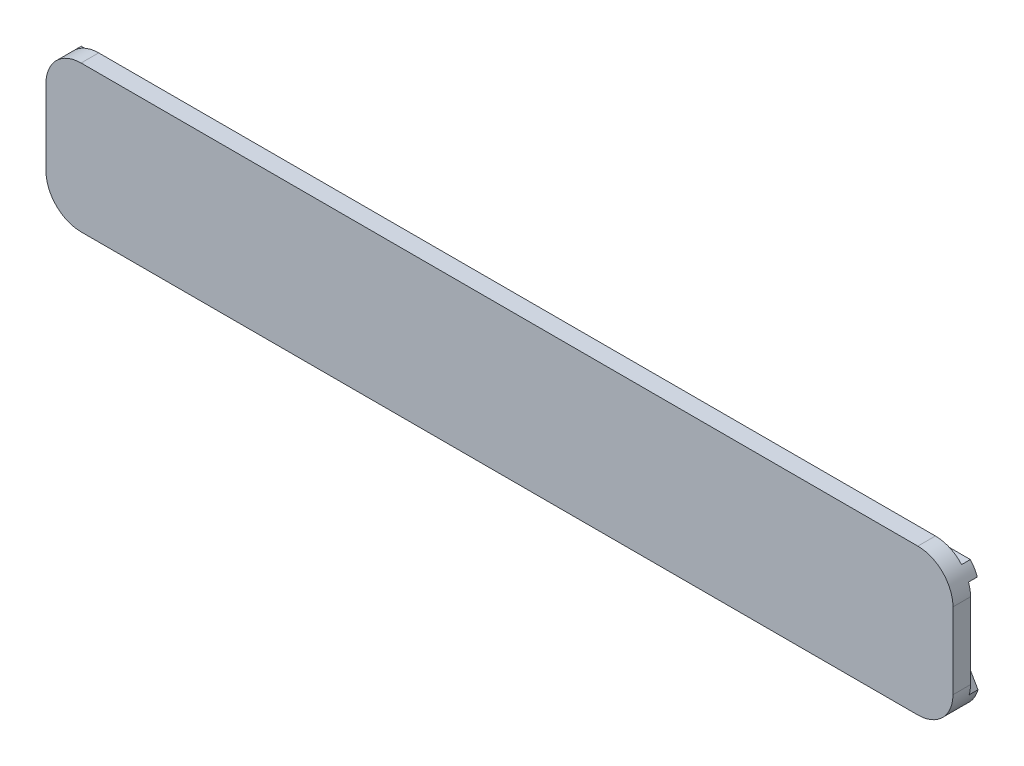
SolidWorks part; units mm, degrees
ref_plane "Front Plane" through (0, 0, 0) normal (0, 0, 1) x (1, 0, 0)
ref_plane "Top Plane" through (0, 0, 0) normal (0, 1, 0) x (1, 0, 0)
ref_plane "Right Plane" through (0, 0, 0) normal (1, 0, 0) x (0, 0, -1)
sketch "Sketch1" plane through (0, 0, 0) normal (0, 0, 1) x (1, 0, 0)
  line L0 (0, 0) -> (55.7, 0) construction
  line L1 (-49.65, 12.5) -> (105.35, 12.5)
  line L2 (-49.65, 12.5) -> (-49.65, -12.5)
  line L3 (-49.65, -12.5) -> (105.35, -12.5)
  line L4 (105.35, 12.5) -> (105.35, -12.5)
  circle A0 centre (55.7, 0) radius 3 construction
  circle A1 centre (0, 0) radius 3 construction
  circle A2 centre (55.7, 0) radius 3 construction
  circle A3 centre (0, 0) radius 3 construction
  circle A4 centre (0, 0) radius 3.3
  circle A5 centre (55.7, 0) radius 3.3
  point P14 (27.85, 0)
  point P15 (27.85, 12.5)
  point P16 (105.35, 0)
  dimension "D2" = 25
  dimension "D3" = 155
  dimension "D1" = 0.3
extrude "Boss-Extrude1" add sketch "Sketch1" against normal blind 2
sketch "Sketch2" plane through (0, 0, 0) normal (0, 0, 1) x (1, 0, 0)
  line L4 (-49.65, 12.5) -> (-49.65, -12.5)
  line L5 (-49.65, -12.5) -> (105.35, -12.5)
  line L6 (105.35, -12.5) -> (105.35, 12.5)
  line L7 (105.35, 12.5) -> (-49.65, 12.5)
  line L8 (-49.65, 12.5) -> (-49.65, -12.5)
  line L9 (-49.65, -12.5) -> (105.35, -12.5)
  line L10 (105.35, -12.5) -> (105.35, 12.5)
  line L11 (105.35, 12.5) -> (-49.65, 12.5)
  dimension "D1" = 0
extrude "Boss-Extrude2" add sketch "Sketch2" along normal blind 1
sketch "Sketch5" plane through (0, 0, -2) normal (0, 0, -1) x (-1, 0, 0)
  line L0 (-105.35, 0) -> (49894.65, 0) construction
  line L1 (-105.35, -12.5) -> (-105.35, 12.5) construction
  line L2 (49.65, 12.5) -> (49.65, -12.5) construction
  line L3 (-27.85, -10.5) -> (-27.85, -8.5)
  line L4 (-105.35, 10.5) -> (-27.85, 10.5)
  line L5 (-105.35, 10.5) -> (-105.35, 8.5)
  line L6 (-105.35, 8.5) -> (-95.535, 8.5)
  line L7 (-27.85, 10.5) -> (-27.85, 8.5)
  line L8 (-103.0406, -8.5) -> (-81.4107, -8.5)
  line L9 (-105.35, -10.5) -> (-105.35, -8.5)
  line L10 (-105.35, -10.5) -> (-27.85, -10.5)
  line L11 (-105.35, 12.5) -> (49.65, 12.5) construction
  line L12 (-105.35, -8.5) -> (-95.535, 8.5)
  line L13 (-93.2256, 8.5) -> (-91.2256, 8.5)
  line L14 (-88.9162, 8.5) -> (-79.1013, -8.5)
  line L15 (-79.1013, -8.5) -> (-77.1013, -8.5)
  line L16 (-74.7919, -8.5) -> (-64.9769, 8.5)
  line L17 (-103.0406, -8.5) -> (-93.2256, 8.5)
  line L18 (-93.2256, 8.5) -> (-91.2256, 8.5)
  line L19 (-91.2256, 8.5) -> (-81.4107, -8.5)
  line L20 (-77.1013, -8.5) -> (-67.2863, 8.5)
  line L21 (-40.9744, 8.5) -> (-31.1594, -8.5)
  line L23 (-28.85, -8.5) -> (-38.665, 8.5)
  line L25 (-93.2256, 8.5) -> (-91.2256, 8.5)
  line L26 (-88.9162, 8.5) -> (-67.2863, 8.5)
  line L27 (-79.1013, -8.5) -> (-77.1013, -8.5)
  line L28 (-74.7919, -8.5) -> (-49.6, -8.5)
  line L29 (-64.9769, 8.5) -> (-45.0449, 8.5)
  line L30 (-38.665, 8.5) -> (-27.85, 8.5)
  line L31 (-28.85, -8.5) -> (-27.85, -8.5)
  line L32 (-45.0449, 8.5) -> (-49.6, -8.5)
  line L34 (-47.5295, -8.5) -> (-42.9744, 8.5)
  line L35 (-42.9744, 8.5) -> (-40.9744, 8.5)
  line L36 (-47.5295, -8.5) -> (-31.1594, -8.5)
  point P4 (-105.35, 0)
  point P7 (49.65, 0)
  point P34 (-27.85, 12.5)
  line M32 (-105.35, 12.5) -> (-105.35, -12.5)
  dimension "D1" = 2
  dimension "D2" = 2
  dimension "D3" = 2
  dimension "D4" = 2
  dimension "D5" = 2
  dimension "D6" = 2
  dimension "D7" = 60
  dimension "D8" = 2
  dimension "D9" = 1
  dimension "D10" = 2
  dimension "D11" = 45
extrude "Boss-Extrude4" add sketch "Sketch5" along normal blind 1.5 contours L12 L0 L17 L13 L19 L14 L26 L20 L16 L29 L21 L23 L30 L7 L4 L6 M32 | L0 L12 L10 L3 L31 L23 L21 L28 L16 L20 L15 L14 L19 L8 L17 M32 region at (66.9728, 7.4905, -2) region at (99.2878, -0.7821, -2)
ref_plane "Plane1" through (27.85, 0, 0) normal (1, 0, 0) x (0, 0, -1)
mirror "Mirror1" about plane through (27.85, 0, 0) normal (1, 0, 0) of "Boss-Extrude4"
fillet "Fillet1" radius 6 4 edges at (105.35, 12.5, -0.5) (105.35, -12.5, -0.5) (-49.65, -12.5, -0.5) (-49.65, 12.5, -0.5)
sketch "Sketch3" plane through (0, 0, 1) normal (0, 0, 1) x (1, 0, 0)
  line L0 (-49.65, -5) -> (105.35, -5) construction
  line L1 (-43.65, -12.5) -> (99.35, -12.5) construction
  line L2 (-49.65, 6.5) -> (-49.65, -6.5) construction
  text T0 "ED Robotics" font "Century Gothic" height 10
  point P7 (27.85, -12.5)
  point P8 (27.85, -5)
  point P9 (-15.5966, -4.6628)
  point P10 (0, 0)
  dimension "D1" = 5
extrude "Engraved team name" [suppressed] cut sketch "Sketch3" against normal blind 0.5
equation "\"D3@Sketch5\"=\"D1@Sketch5\""
equation "\"D4@Sketch5\"=\"D3@Sketch5\""
equation "\"D5@Sketch5\"=\"D3@Sketch5\""
equation "\"D6@Sketch5\"=\"D3@Sketch5\""
equation "\"D8@Sketch5\"=\"D3@Sketch5\""
equation "\"D9@Sketch5\"=\"D3@Sketch5\"/2"
equation "\"D10@Sketch5\"=\"D3@Sketch5\""
